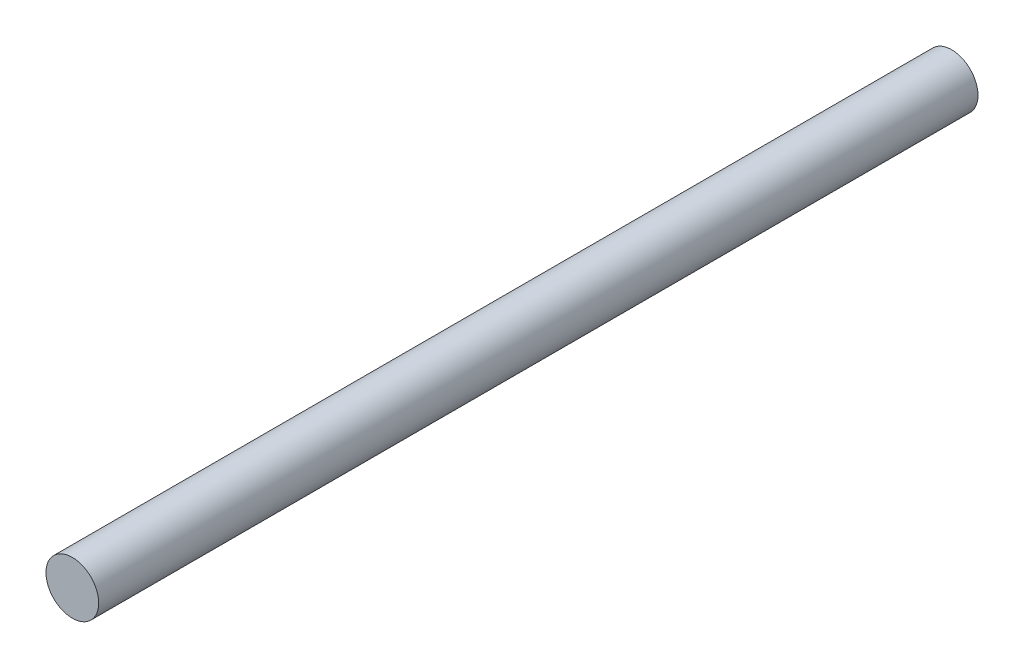
SolidWorks part; units mm, degrees
material "Alloy Steel"
ref_plane "Front Plane" through (0, 0, 0) normal (0, 0, 1) x (1, 0, 0)
ref_plane "Top Plane" through (0, 0, 0) normal (0, 1, 0) x (1, 0, 0)
ref_plane "Right Plane" through (0, 0, 0) normal (1, 0, 0) x (0, 0, -1)
sketch "Sketch1" plane through (0, 0, 0) normal (0, 0, 1) x (1, 0, 0)
  circle A0 centre (0, 0) radius 3
  dimension "D1" = 6
extrude "Boss-Extrude1" add sketch "Sketch1" along normal blind 100
ref_axis "Axis1" through (0, 0, 100) along (0, 0, -1)
